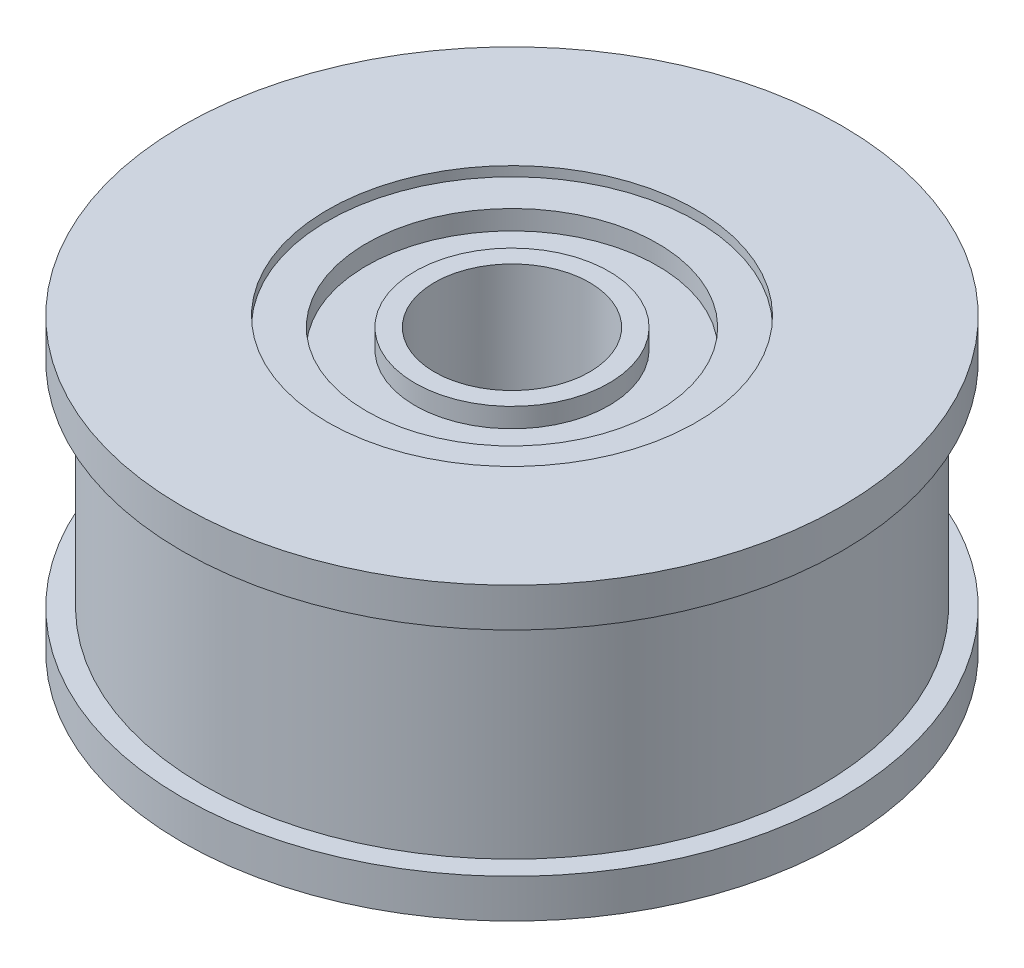
SolidWorks part; units mm, degrees
ref_plane "前视基准面" through (0, 0, 0) normal (0, 0, 1) x (1, 0, 0)
ref_plane "上视基准面" through (0, 0, 0) normal (0, 1, 0) x (1, 0, 0)
ref_plane "右视基准面" through (0, 0, 0) normal (1, 0, 0) x (0, 0, -1)
sketch "草图1" plane through (0, 0, 0) normal (0, 1, 0) x (1, 0, 0)
  circle A0 centre (0, 0) radius 15.915
  dimension "D1" = 31.83
extrude "凸台-拉伸1" add sketch "草图1" along normal blind 11
sketch "草图2" plane through (0, 11, 0) normal (0, 1, 0) x (1, 0, 0)
  circle A0 centre (0, 0) radius 17
  dimension "D1" = 34
extrude "凸台-拉伸2" add sketch "草图2" along normal blind 2
sketch "草图3" plane through (0, 0, 0) normal (0, -1, 0) x (1, 0, 0)
  circle A0 centre (0, 0) radius 17
  dimension "D1" = 34
extrude "凸台-拉伸3" add sketch "草图3" along normal blind 2
sketch "草图4" plane through (0, -2, 0) normal (0, -1, 0) x (1, 0, 0)
  circle A0 centre (0, 0) radius 9.5
  circle A1 centre (0, 0) radius 4
  circle A2 centre (0, 0) radius 5
  circle A3 centre (0, 0) radius 7.5
  dimension "D1" = 19
  dimension "D2" = 8
  dimension "D3" = 10
  dimension "D4" = 15
extrude "切除-拉伸1" cut sketch "草图4" against normal blind 0.5 contours A0 | A3
extrude "切除-拉伸2" cut sketch "草图4<3>" against normal blind 1.5 contours A3 A2 region at (-7.2879, -2, 0)
sketch "草图4<3>" plane through (0, -2, 0) normal (0, -1, 0) x (1, 0, 0) same geometry as "草图4"
extrude "切除-拉伸3" cut sketch "草图4<4>" against normal blind 0.5 contours A2 A1 region at (-4.8586, -2, 0)
sketch "草图4<4>" plane through (0, -2, 0) normal (0, -1, 0) x (1, 0, 0) same geometry as "草图4"
extrude "切除-拉伸4" cut sketch "草图4<5>" against normal through all contours A1 region at (0, -2, 0)
sketch "草图4<5>" plane through (0, -2, 0) normal (0, -1, 0) x (1, 0, 0) same geometry as "草图4"
sketch "草图6" plane through (0, 13, 0) normal (0, 1, 0) x (1, 0, 0)
  circle A0 centre (0, 0) radius 4
  circle A1 centre (0, 0) radius 5
  circle A2 centre (0, 0) radius 7.5
  circle A3 centre (0, 0) radius 9.5
  circle M1 centre (0, 0) radius 4
  dimension "D1" = 8
  dimension "D2" = 10
  dimension "D3" = 19
  dimension "D4" = 15
extrude "切除-拉伸5" cut sketch "草图6" against normal blind 0.5 contours A3 A2 region at (-9.2313, 13, 0)
extrude "切除-拉伸6" cut sketch "草图6<3>" against normal blind 1.5 contours A2 A1 region at (-7.2879, 13, 0)
sketch "草图6<3>" plane through (0, 13, 0) normal (0, 1, 0) x (1, 0, 0) same geometry as "草图6"
extrude "切除-拉伸7" cut sketch "草图6<5>" against normal blind 0.5 contours A1 M1 region at (-4.8586, 13, 0)
sketch "草图6<5>" plane through (0, 13, 0) normal (0, 1, 0) x (1, 0, 0) same geometry as "草图6"
